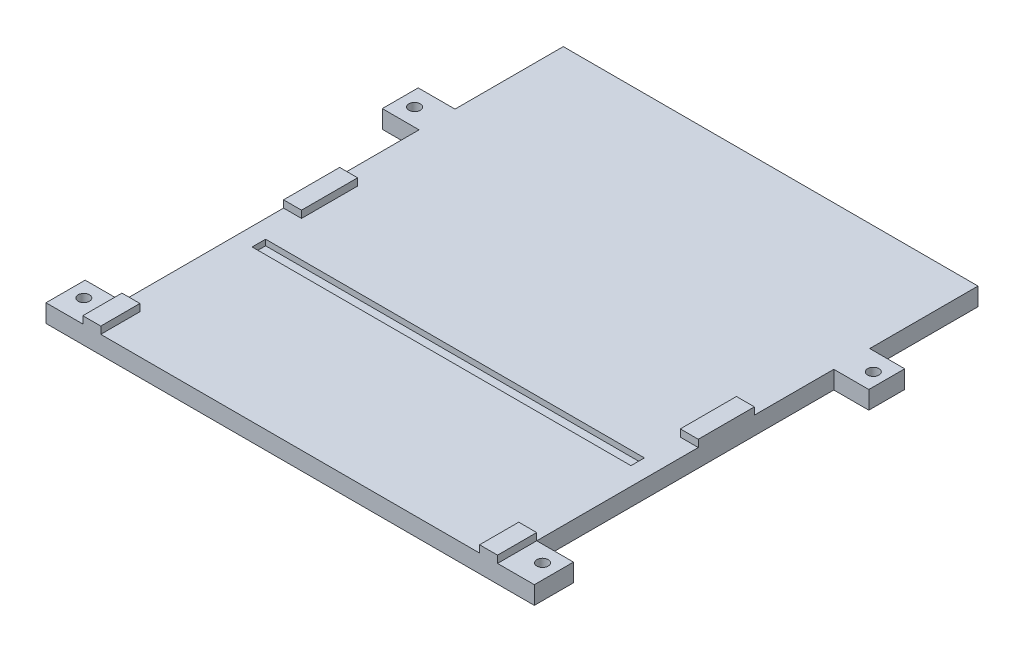
SolidWorks part; units mm, degrees
ref_plane "Front Plane" through (0, 0, 0) normal (0, 0, 1) x (1, 0, 0)
ref_plane "Top Plane" through (0, 0, 0) normal (0, 1, 0) x (1, 0, 0)
ref_plane "Right Plane" through (0, 0, 0) normal (1, 0, 0) x (0, 0, -1)
sketch "Sketch1" plane through (0, 0, 0) normal (0, 1, 0) x (1, 0, 0)
  line L1 (-105.5, 55) -> (105.5, 55)
  line L2 (-105.5, 55) -> (-105.5, -55)
  line L3 (-105.5, -55) -> (105.5, -55)
  line L4 (105.5, 55) -> (105.5, -55)
  line L5 (-105.5, 55) -> (105.5, -55) construction
  line L6 (-105.5, -55) -> (105.5, 55) construction
  line L7 (-105.5, 55) -> (-115.5, 55)
  line L8 (-105.5, 55) -> (-105.5, -55)
  line L9 (-105.5, -55) -> (-115.5, -55)
  line L10 (-115.5, 55) -> (-115.5, -55)
  line L11 (105.5, 55) -> (115.5, 55)
  line L12 (105.5, 55) -> (105.5, -55)
  line L13 (105.5, -55) -> (115.5, -55)
  line L14 (115.5, 55) -> (115.5, -55)
  point P0 (0, 0)
  dimension "D1" = 211
  dimension "D2" = 110
  dimension "D3" = 10
  dimension "D4" = 10
extrude "Boss-Extrude1" add sketch "Sketch1" along normal blind 10 contours L4 L1 L2 L3 region at (0, 0, 0)
extrude "Boss-Extrude2" add sketch "Sketch1<3>" along normal blind 14 contours L7 L10 L9 L2 | L14 L11 L4 L13 region at (-110.5, 0, 0) region at (110.5, 0, 0)
sketch "Sketch1<3>" plane through (0, 0, 0) normal (0, 1, 0) x (1, 0, 0) same geometry as "Sketch1"
sketch "Sketch5" plane through (0, 10, 0) normal (0, 1, 0) x (1, 0, 0)
  line L0 (-105.5, 0) -> (105.5, 0) construction
  line L1 (-105.5, 55) -> (-105.5, -55) construction
  line L2 (105.5, 55) -> (105.5, -55) construction
  line L4 (-105.5, 3.75) -> (105.5, 3.75)
  line L5 (-105.5, 3.75) -> (-105.5, -3.75)
  line L6 (-105.5, -3.75) -> (105.5, -3.75)
  line L7 (105.5, 3.75) -> (105.5, -3.75)
  line L8 (-105.5, 3.75) -> (105.5, -3.75) construction
  line L9 (-105.5, -3.75) -> (105.5, 3.75) construction
  point P6 (0, 0)
  dimension "D1" = 7.5
extrude "Cut-Extrude5" cut sketch "Sketch5" against normal blind 3.2
sketch "Sketch6" plane through (0, 0, 0) normal (0, 1, 0) x (1, 0, 0)
  line L0 (-105.5, 55) -> (-115.5, 55) construction
  line L1 (-136, 119.2432) -> (-106.5, 119.2432)
  line L2 (-136, 119.2432) -> (-136, 99.2432)
  line L3 (-136, 99.2432) -> (-115.5, 99.2432)
  line L4 (135, 119.2432) -> (135, 99.2432)
  line L5 (-136, 119.2432) -> (135, 99.2432) construction
  line L6 (-136, 99.2432) -> (135, 119.2432) construction
  line L7 (105.5, 55) -> (115.5, 55) construction
  line L8 (-115.5, 55) -> (-115.5, -55) construction
  line L9 (115.5, 55) -> (115.5, -55) construction
  line L10 (-136, -66.2523) -> (-115.5, -66.2523)
  line L12 (136, -66.2523) -> (115.5, -66.2523)
  line L13 (104.5, 119.2432) -> (135, 119.2432)
  line L14 (-115.5, 0) -> (115.5, 0) construction
  line L15 (-115.5, 55) -> (-115.5, 99.2432)
  line L16 (115.5, 55) -> (115.5, 99.2432)
  line L17 (-115.5, 55) -> (115.5, 55)
  line L18 (115.5, 99.2432) -> (135, 99.2432)
  line L20 (-136, -66.2523) -> (-136, -88.0654)
  line L21 (-136, -88.0654) -> (136, -88.0654)
  line L22 (136, -88.0654) -> (136, -66.2523)
  line L23 (-115.5, -66.2523) -> (-115.5, -55)
  line L24 (-104.1001, -55) -> (104.5, -55)
  line L25 (-106.5, 119.2432) -> (104.5, 119.2432)
  line L27 (-115.5, -55) -> (-104.1001, -55)
  line L28 (104.5, -55) -> (115.5, -55)
  line L29 (115.5, -55) -> (115.5, -66.2523)
  circle A0 centre (-127.75, 109) radius 3.15
  circle A1 centre (127.75, 109) radius 3.15
  circle A2 centre (-127.75, -75.2539) radius 3.15
  circle A3 centre (127.75, -75.2539) radius 3.15
  point P0 (-0.5, 109.2432)
  point P34 (-0.5, -109.2432)
  dimension "D4" = 6.3
  dimension "D6" = 6.3
  dimension "D10" = 6.3
  dimension "D11" = 6.3
  dimension "D1" = 136
  dimension "D2" = 135
  dimension "D3" = 20
  dimension "D5" = 12.25
  dimension "D7" = 12.25
  dimension "D8" = 54
  dimension "D9" = 54
  dimension "D12" = 136
extrude "Boss-Extrude3" add sketch "Sketch6" along normal blind 10
sketch "Sketch7" plane through (0, 0, 0) normal (0, -1, 0) x (1, 0, 0)
  line L1 (-127.75, 69.3649) -> (-122.65, 72.3094)
  line L2 (-122.65, 72.3094) -> (-122.65, 78.1984)
  line L3 (-122.65, 78.1984) -> (-127.75, 81.1429)
  line L4 (-127.75, 81.1429) -> (-132.85, 78.1984)
  line L5 (-132.85, 78.1984) -> (-132.85, 72.3094)
  line L6 (-132.85, 72.3094) -> (-127.75, 69.3649)
  line L7 (127.75, 69.3649) -> (132.85, 72.3094)
  line L8 (132.85, 72.3094) -> (132.85, 78.1984)
  line L9 (132.85, 78.1984) -> (127.75, 81.1429)
  line L10 (127.75, 81.1429) -> (122.65, 78.1984)
  line L11 (122.65, 78.1984) -> (122.65, 72.3094)
  line L12 (122.65, 72.3094) -> (127.75, 69.3649)
  line L13 (-127.75, -114.889) -> (-122.65, -111.9445)
  line L14 (-122.65, -111.9445) -> (-122.65, -106.0555)
  line L15 (-122.65, -106.0555) -> (-127.75, -103.111)
  line L16 (-127.75, -103.111) -> (-132.85, -106.0555)
  line L17 (-132.85, -106.0555) -> (-132.85, -111.9445)
  line L18 (-132.85, -111.9445) -> (-127.75, -114.889)
  line L19 (127.75, -114.889) -> (132.85, -111.9445)
  line L20 (132.85, -111.9445) -> (132.85, -106.0555)
  line L21 (132.85, -106.0555) -> (127.75, -103.111)
  line L22 (127.75, -103.111) -> (122.65, -106.0555)
  line L23 (122.65, -106.0555) -> (122.65, -111.9445)
  line L24 (122.65, -111.9445) -> (127.75, -114.889)
  circle A0 centre (-127.75, 75.2539) radius 5.1 construction
  circle A1 centre (127.75, 75.2539) radius 5.1 construction
  circle A2 centre (-127.75, -109) radius 5.1 construction
  circle A3 centre (127.75, -109) radius 5.1 construction
  dimension "D1" = 10.2
  dimension "D2" = 10.2
  dimension "D3" = 10.2
  dimension "D4" = 10.2
extrude "Cut-Extrude9" cut sketch "Sketch7<2>" against normal blind 2
sketch "Sketch7<2>" plane through (0, 0, 0) normal (0, -1, 0) x (1, 0, 0) same geometry as "Sketch7"
sketch "Sketch11" plane through (0, 10, 0) normal (0, 1, 0) x (1, 0, 0)
  line L0 (-136, -88.0654) -> (136, -88.0654) construction
  line L1 (-115.5, -66.2523) -> (-105.5, -66.2523)
  line L2 (-115.5, -66.2523) -> (-115.5, -88.0654)
  line L3 (-115.5, -88.0654) -> (-105.5, -88.0654)
  line L4 (-105.5, -66.2523) -> (-105.5, -88.0654)
  line L6 (115.5, -66.2523) -> (105.5, -66.2523)
  line L7 (115.5, -66.2523) -> (115.5, -88.0654)
  line L8 (115.5, -88.0654) -> (105.5, -88.0654)
  line L9 (105.5, -66.2523) -> (105.5, -88.0654)
  dimension "D1" = 10
  dimension "D2" = 10
extrude "Boss-Extrude5" add sketch "Sketch11" along normal blind 4
sketch "Sketch12" plane through (0, 14, 0) normal (0, 1, 0) x (1, 0, 0)
  line L0 (-115.5, 55) -> (-115.5, -55) construction
  line L1 (-115.5, 23.75) -> (-105.5, 23.75)
  line L2 (-115.5, 23.75) -> (-115.5, -55)
  line L3 (-115.5, -55) -> (-105.5, -55)
  line L4 (-105.5, 23.75) -> (-105.5, -55)
  line L5 (105.5, 55) -> (105.5, 3.75) construction
  line L6 (105.5, 23.75) -> (115.5, 23.75)
  line L7 (105.5, 23.75) -> (105.5, -55)
  line L8 (105.5, -55) -> (115.5, -55)
  line L9 (115.5, 23.75) -> (115.5, -55)
  line L10 (105.5, 3.75) -> (-105.5, 3.75) construction
  line L11 (105.5, 3.75) -> (-105.5, 3.75) construction
  dimension "D1" = 20
  dimension "D2" = 20
extrude "Cut-Extrude10" cut sketch "Sketch12" against normal blind 4
extrude "Cut-Extrude7" cut sketch "Sketch7" against normal blind 3
sketch "Sketch13" plane through (0, 0, 0) normal (0, 1, 0) x (1, 0, 0)
  line L0 (135, 119.2432) -> (-136, 119.2432) construction
  line L1 (-115.5, 119.2432) -> (115.5, 119.2432)
  line L2 (-115.5, 119.2432) -> (-115.5, 179.5557)
  line L3 (-115.5, 179.5557) -> (115.5, 179.5557)
  line L4 (115.5, 119.2432) -> (115.5, 179.5557)
extrude "Boss-Extrude6" add sketch "Sketch13" along normal blind 10
